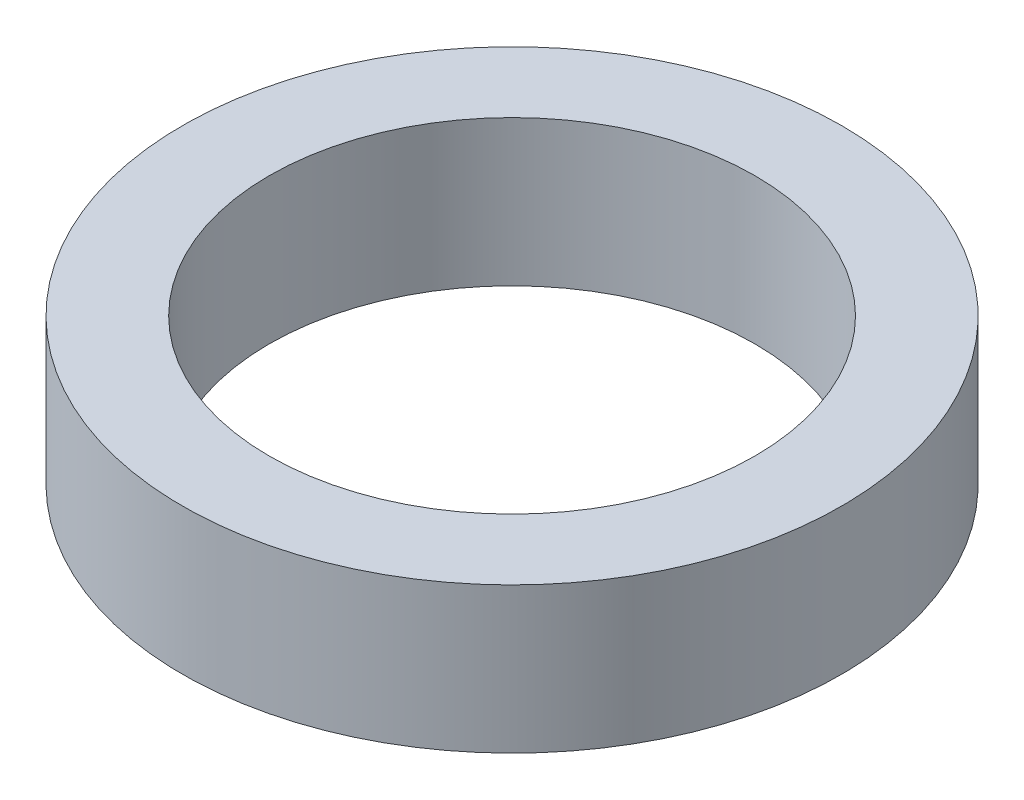
SolidWorks part; units mm, degrees
ref_plane "Front Plane" through (0, 0, 0) normal (0, 0, 1) x (1, 0, 0)
ref_plane "Top Plane" through (0, 0, 0) normal (0, 1, 0) x (1, 0, 0)
ref_plane "Right Plane" through (0, 0, 0) normal (1, 0, 0) x (0, 0, -1)
sketch "Sketch1" plane through (0, 0, 0) normal (0, 1, 0) x (1, 0, 0)
  circle A0 centre (0, 0) radius 47.5
  dimension "FLANGE_OD" = 95
extrude "Boss-Extrude1" add sketch "Sketch1" along normal blind 21
sketch "Sketch2" plane through (0, 0, 0) normal (0, 1, 0) x (1, 0, 0)
  circle A0 centre (0, 0) radius 35
  dimension "BORE_D" = 70
extrude "Cut-Extrude1" cut sketch "Sketch2" along normal through all
sketch "Sketch3" plane through (0, 21, 0) normal (0, 1, 0) x (1, 0, 0)
  circle A0 centre (0, 0) radius 21.5232 construction
  circle A1 centre (-21.5232, 0) radius 2.2352
  dimension "BOLT_D" = 4.4705
  dimension "BOLT_PCD" = 43.0464
extrude "Cut-Extrude2" cut sketch "Sketch3" against normal blind 15.9252 rebuild error yes
pattern_circular "CirPattern1" count 3 over 360 rebuild error yes
